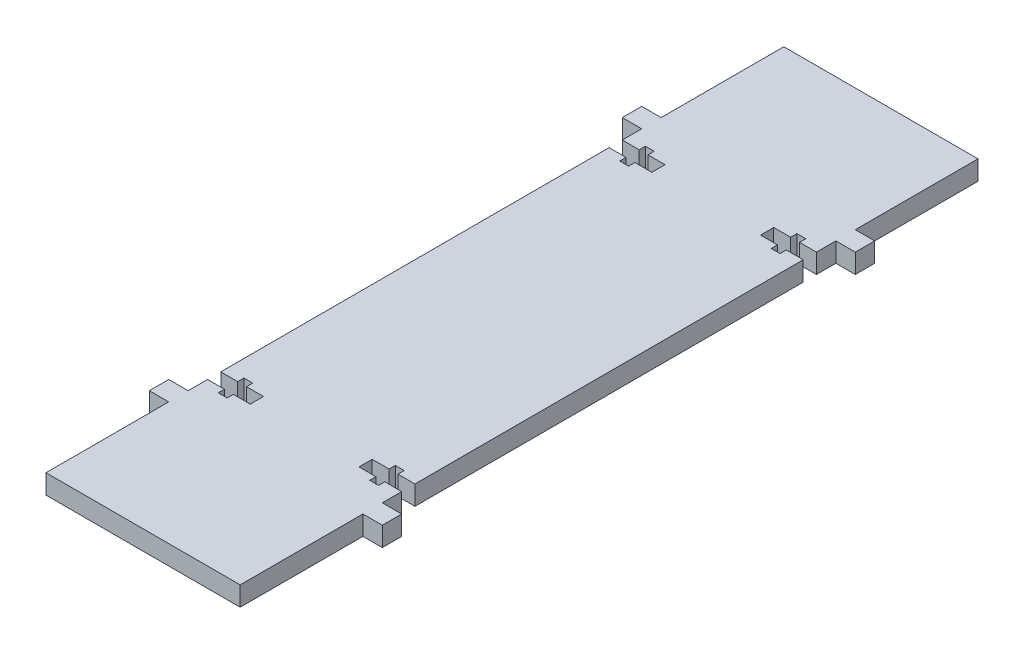
SolidWorks part; units mm, degrees
ref_plane "Front Plane" through (0, 0, 0) normal (0, 0, 1) x (1, 0, 0)
ref_plane "Top Plane" through (0, 0, 0) normal (0, 1, 0) x (1, 0, 0)
ref_plane "Right Plane" through (0, 0, 0) normal (1, 0, 0) x (0, 0, -1)
sketch "Elevator Belt Backplate" plane through (0, 0, 0) normal (0, 1, 0) x (1, 0, 0)
  line L0 (-31.75, 0) -> (31.75, 0) construction
  line L1 (-31.75, -120.65) -> (31.75, -120.65)
  line L2 (-31.75, -120.65) -> (-31.75, -80.518)
  line L3 (-31.75, 120.65) -> (31.75, 120.65)
  line L4 (31.75, -120.65) -> (31.75, -80.518)
  line L5 (-31.75, -120.65) -> (31.75, 120.65) construction
  line L6 (-31.75, 120.65) -> (31.75, -120.65) construction
  line L7 (31.75, 80.518) -> (31.75, 120.65)
  line L8 (31.75, 74.168) -> (38.1, 74.168)
  line L9 (0, 120.65) -> (0, -120.65) construction
  line L10 (31.75, 80.518) -> (38.1, 80.518)
  line L11 (38.1, 74.168) -> (38.1, 80.518)
  line L12 (31.75, -80.518) -> (38.1, -80.518)
  line L13 (38.1, -74.168) -> (38.1, -80.518)
  line L14 (31.75, -74.168) -> (38.1, -74.168)
  line L15 (-31.75, 80.518) -> (-38.1, 80.518)
  line L16 (-31.75, -74.168) -> (-38.1, -74.168)
  line L17 (-38.1, -74.168) -> (-38.1, -80.518)
  line L18 (-31.75, -80.518) -> (-38.1, -80.518)
  line L19 (-38.1, 74.168) -> (-38.1, 80.518)
  line L20 (-31.75, 74.168) -> (-38.1, 74.168)
  line L21 (-31.75, 80.518) -> (-31.75, 120.65)
  line L22 (-31.75, -74.168) -> (-31.75, -67.818)
  line L23 (31.75, -74.168) -> (31.75, -67.818)
  line L24 (-31.75, 67.818) -> (-26.215, 67.818)
  line L25 (-26.215, 67.818) -> (-26.215, 69.859)
  line L26 (-26.215, 69.859) -> (-23.315, 69.859)
  line L27 (-23.315, 69.859) -> (-23.315, 67.818)
  line L28 (-23.315, 67.818) -> (-17.78, 67.818)
  line L29 (-17.78, 67.818) -> (-17.78, 63.5)
  line L30 (-17.78, 63.5) -> (-23.315, 63.5)
  line L31 (-23.315, 63.5) -> (-23.315, 61.459)
  line L32 (-23.315, 61.459) -> (-26.215, 61.459)
  line L33 (-26.215, 61.459) -> (-26.215, 63.5)
  line L34 (-26.215, 63.5) -> (-31.75, 63.5)
  line L35 (-31.75, 67.818) -> (-31.75, 74.168)
  line L36 (31.75, 67.818) -> (26.215, 67.818)
  line L37 (23.315, 69.859) -> (23.315, 67.818)
  line L38 (26.215, 67.818) -> (26.215, 69.859)
  line L39 (26.215, 69.859) -> (23.315, 69.859)
  line L40 (23.315, 67.818) -> (17.78, 67.818)
  line L41 (26.215, 63.5) -> (31.75, 63.5)
  line L42 (26.215, 61.459) -> (26.215, 63.5)
  line L43 (23.315, 61.459) -> (26.215, 61.459)
  line L44 (23.315, 63.5) -> (23.315, 61.459)
  line L45 (17.78, 63.5) -> (23.315, 63.5)
  line L46 (17.78, 67.818) -> (17.78, 63.5)
  line L47 (31.75, 67.818) -> (31.75, 74.168)
  line L48 (26.215, -63.5) -> (31.75, -63.5)
  line L49 (31.75, -67.818) -> (26.215, -67.818)
  line L50 (17.78, -63.5) -> (23.315, -63.5)
  line L51 (17.78, -67.818) -> (17.78, -63.5)
  line L52 (23.315, -67.818) -> (17.78, -67.818)
  line L53 (23.315, -63.5) -> (23.315, -61.459)
  line L54 (23.315, -61.459) -> (26.215, -61.459)
  line L55 (26.215, -61.459) -> (26.215, -63.5)
  line L56 (26.215, -69.859) -> (23.315, -69.859)
  line L57 (26.215, -67.818) -> (26.215, -69.859)
  line L58 (23.315, -69.859) -> (23.315, -67.818)
  line L59 (-17.78, -67.818) -> (-17.78, -63.5)
  line L60 (-26.215, -63.5) -> (-31.75, -63.5)
  line L61 (-26.215, -61.459) -> (-26.215, -63.5)
  line L62 (-23.315, -61.459) -> (-26.215, -61.459)
  line L63 (-23.315, -63.5) -> (-23.315, -61.459)
  line L64 (-17.78, -63.5) -> (-23.315, -63.5)
  line L65 (-23.315, -67.818) -> (-17.78, -67.818)
  line L66 (-23.315, -69.859) -> (-23.315, -67.818)
  line L67 (-26.215, -69.859) -> (-23.315, -69.859)
  line L68 (-26.215, -67.818) -> (-26.215, -69.859)
  line L69 (-31.75, -67.818) -> (-26.215, -67.818)
  line L70 (31.75, -63.5) -> (31.75, 63.5)
  line L71 (-31.75, -63.5) -> (-31.75, 63.5)
  point P0 (0, 0)
  dimension "D1" = 6.35
  dimension "D2" = 6.35
  dimension "D3" = 6.35
  dimension "D4" = 63.5
  dimension "D5" = 241.3
  dimension "D6" = 4.318
  dimension "D7" = 2.9
  dimension "D8" = 8.4
  dimension "D9" = 13.97
  dimension "D10" = 63.5
extrude "Boss-Extrude1" add sketch "Elevator Belt Backplate" along normal blind 6.35
equation "\"Ball Diameter\"= 1.75in"
equation "\"Sheet Thickness\"= 0.25in"
equation "\"Screw Diameter\"= .17in"
equation "\"Robot Diameter\"= 14in"
equation "\"Castor Screw Diameter\"= 0.22in"
equation "\"Wheel Diameter\" = 4in"
equation "\"Nut Diameter\" = 8.4mm"
equation "\"Nut Height\" = 2.9mm"
equation "\"Screw Height\" = 0.55in"
equation "\"Pulley Diameter\" = 1in"
equation "\"Reactor Height\" = 14in"
equation "\"Elevator Height\" = 11.5in"
equation "\"Elevator Width\" = \"Ball Diameter\" + 0.25in"
equation "\"Elevator Bearing Diameter\" = sqr(2*(\"Sheet Thickness\"^2)) + 0.2in"
equation "\"Elevator Axle Length\" = \"Elevator Width\" + 8*\"Sheet Thickness\""
equation "\"D7@Elevator Belt Backplate\"=\"Sheet Thickness\""
equation "\"D8@Elevator Belt Backplate\"=\"Sheet Thickness\""
equation "\"D4@Elevator Belt Backplate\"=\"Elevator Width\" + 2 * \"Sheet Thickness\""
equation "\"D5@Elevator Belt Backplate\"=\"Elevator Height\"-\"Pulley Diameter\"-1in"
equation "\"D1@Boss-Extrude1\"=\"Sheet Thickness\""
equation "\"D6@Elevator Belt Backplate\" = \"Screw Diameter\""
equation "\"D7@Elevator Belt Backplate\"=\"Nut Height\""
equation "\"D8@Elevator Belt Backplate\"=\"Nut Diameter\""
equation "\"D9@Elevator Belt Backplate\"=\"Screw Height\""
